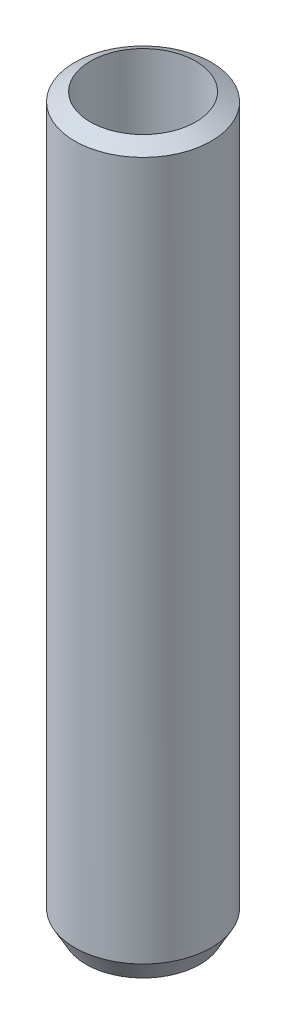
SolidWorks part; units mm, degrees
ref_plane "Front Plane" through (0, 0, 0) normal (0, 0, 1) x (1, 0, 0)
ref_plane "Top Plane" through (0, 0, 0) normal (0, 1, 0) x (1, 0, 0)
ref_plane "Right Plane" through (0, 0, 0) normal (1, 0, 0) x (0, 0, -1)
sketch "Sketch1" plane through (0, 0, 0) normal (0, 1, 0) x (1, 0, 0)
  circle A0 centre (0, 0) radius 35
  dimension "SHAFT_OD" = 70
extrude "Boss-Extrude1" add sketch "Sketch1" along normal blind 374.1555
sketch "Sketch2" plane through (0, 0, 0) normal (0, 1, 0) x (1, 0, 0)
  circle A0 centre (0, 0) radius 27.0104
  dimension "BORE_D" = 54.0209
extrude "Cut-Extrude1" cut sketch "Sketch2" along normal through all
chamfer "Chamfer1" distance 5.7836 angle 60.674 2 edges at (0, 374.1555, 35) (0, 0, 35) first distance on face at (0, 374.1555, 35) first distance on face at (0, 0, 27.0104)
